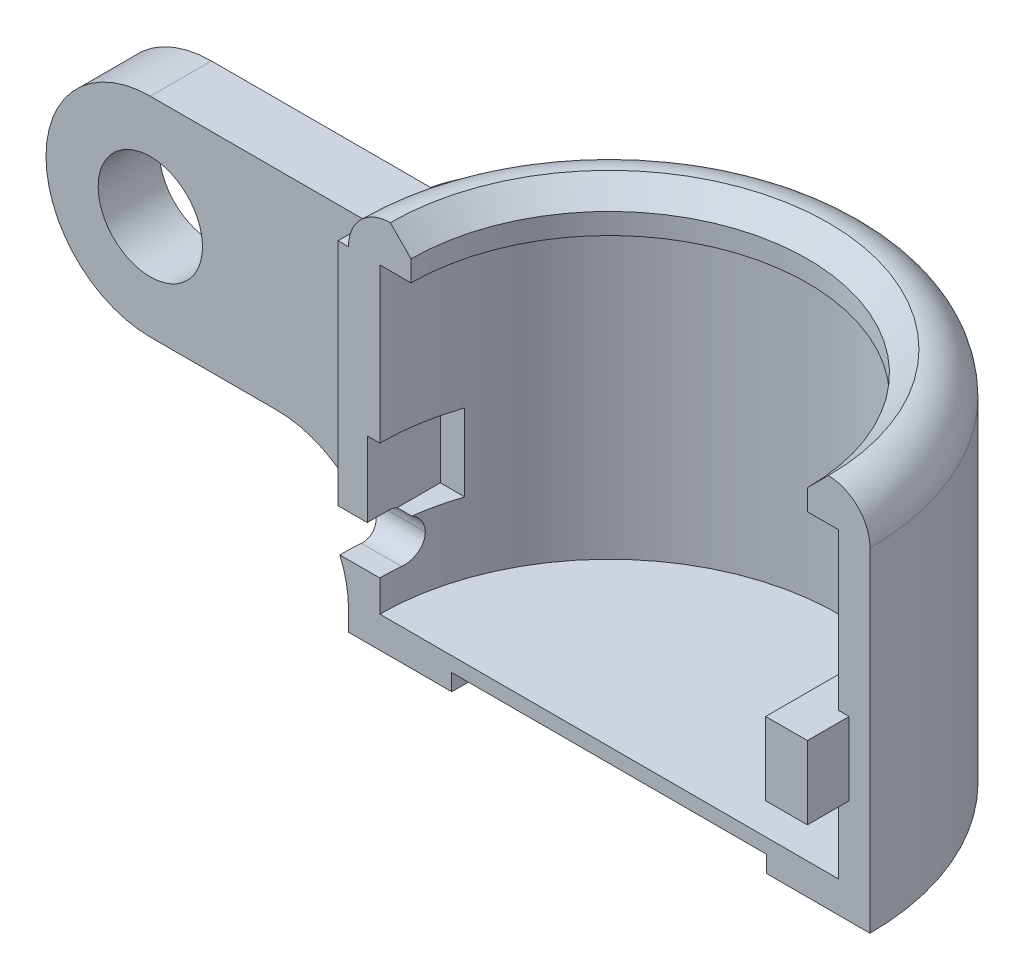
SolidWorks part; units mm, degrees
ref_plane "Plan de face" through (0, 0, 0) normal (0, 0, 1) x (1, 0, 0)
ref_plane "Plan de dessus" through (0, 0, 0) normal (0, 1, 0) x (1, 0, 0)
ref_plane "Plan de droite" through (0, 0, 0) normal (1, 0, 0) x (0, 0, -1)
sketch "Esquisse3" plane through (0, 0, 0) normal (0, 0, 1) x (1, 0, 0)
  line L0 (0, 0) -> (12.5, 0)
  line L1 (12.5, 0) -> (12.5, 18)
  line L2 (12.5, 18) -> (9.5, 18)
  line L3 (9.5, 18) -> (9.5, 16)
  line L4 (9.5, 16) -> (11, 16)
  line L5 (11, 16) -> (11, 1.5)
  line L6 (11, 1.5) -> (0, 1.5)
  line L7 (0, 1.5) -> (0, 0)
  line L8 (0, 0) -> (0, 28.6696) construction
  point P3 (9.5, 19.1495)
  point P11 (9.5, 17.9629)
  dimension "D1" = 19
  dimension "D2" = 25
  dimension "D3" = 14.5
  dimension "D4" = 2
  dimension "D5" = 1.5
  dimension "D6" = 22
revolve "Révolution1" add sketch "Esquisse3" angle 180 about L8
chamfer "Chanfrein1" distance 1 angle 45 1 edges at (0, 18, -9.5)
fillet "Congé1" radius 2 1 edges at (0, 18, -12.5)
sketch "Esquisse4" plane through (0, 0, 0) normal (1, 0, 0) x (0, 0, -1)
  line L0 (0, 0) -> (0, 3) construction
  line L1 (-2, 3) -> (2, 3)
  line L2 (-2, 3) -> (-2, 5)
  line L3 (-2, 5) -> (2, 5)
  line L4 (2, 3) -> (2, 5)
  dimension "D1" = 4
  dimension "D2" = 2
  dimension "D3" = 1.5
extrude "Enlèv. mat.-Extru.1" cut sketch "Esquisse4" against normal up to next
fillet "Congé2" radius 1 2 edges at (-11.5778, 5, -2) (-11.5778, 3, -2)
sketch "Esquisse5" plane through (0, 0, 0) normal (0, 0, 1) x (1, 0, 0)
  line L0 (11, 16) -> (11, 1.5) construction
  line L1 (9.5, 8.5) -> (11.5, 8.5)
  line L2 (9.5, 8.5) -> (9.5, 5)
  line L3 (9.5, 5) -> (11.5, 5)
  line L4 (11.5, 8.5) -> (11.5, 5)
  dimension "D1" = 3.5
  dimension "D2" = 2
  dimension "D3" = 1.5
  dimension "D4" = 3.5
extrude "Boss.-Extru.2" add sketch "Esquisse5" against normal up to surface and the other way blind 2 up to face at (-6.0789, 6.129, -2.9349)
sketch "Esquisse6" plane through (0, 0, 0) normal (0, 0, 1) x (1, 0, 0)
  line L0 (9.5, 5) -> (11.5, 5) construction
  line L1 (-11.5, 5) -> (-9.5, 5)
  line L2 (-11.5, 5) -> (-11.5, 8.5)
  line L3 (-11.5, 8.5) -> (-9.5, 8.5)
  line L4 (-9.5, 5) -> (-9.5, 8.5)
  line L5 (11.5, 8.5) -> (9.5, 8.5) construction
  line L6 (9.5, 8.5) -> (9.5, 5) construction
  line L7 (-12.5, 5) -> (-12.5, 16) construction
  line L9 (-11.6, 8.6) -> (-9.4, 8.6)
  line L10 (-11.6, 8.6) -> (-11.6, 4.9)
  line L11 (-11.6, 4.9) -> (-9.4, 4.9)
  line L12 (-9.4, 8.6) -> (-9.4, 4.9)
  point P16 (0, 0)
  point P17 (0, 0)
  dimension "D1" = 1
  dimension "D2" = 0.1
  dimension "D3" = 0.1
  dimension "D4" = 0.1
  dimension "D5" = 0.1
extrude "Enlèv. mat.-Extru.3" cut sketch "Esquisse6" against normal blind 3.5 contours L9 L12 L11 L10
sketch "Esquisse8" plane through (0, 0, 0) normal (0, -1, 0) x (1, 0, 0)
  line L2 (12.5, 0) -> (-12.5, 0) construction
  line L3 (-7.55, 0) -> (7.55, 0)
  line L4 (-7.55, 0) -> (-7.55, -2.1)
  line L5 (-7.55, -2.1) -> (7.55, -2.1)
  line L6 (7.55, 0) -> (7.55, -2.1)
  point P6 (0, 0)
  dimension "D1" = 2.1
  dimension "D2" = 15.1
extrude "Enlèv. mat.-Extru.4" cut sketch "Esquisse8" against normal blind 0.8
sketch "Esquisse9" plane through (0, 0, 0) normal (0, 1, 0) x (1, 0, 0)
  line L0 (-10.0669, 7.41) -> (-13, 7.41)
  line L1 (-13, 7.41) -> (-13, 4.43)
  line L2 (-13, 4.43) -> (-28.5, 4.43)
  line L3 (-28.5, 4.43) -> (-28.5, 1.5)
  line L4 (-28.5, 1.5) -> (-13, 1.5)
  line L5 (-13, 1.5) -> (-13, 0)
  line L6 (-13, 0) -> (-12.5, 0)
  arc A0 (12.5, 0) -> (-12.5, 0) centre (0, 0) ccw construction
  arc A1 (-12.5, 0) -> (-10.0669, 7.41) centre (0, 0) cw
  dimension "D1" = 16
  dimension "D2" = 1.5
  dimension "D3" = 2.93
  dimension "D4" = 2.98
  dimension "D5" = 0.5
extrude "Boss.-Extru.3" add sketch "Esquisse9" against normal blind 10 from vertex starting at point (-12.5, 16, 0)
fillet "Congé3" radius 5 2 edges at (-28.5, 6, -2.965) (-28.5, 16, -2.965)
sketch "Esquisse10" plane through (0, 0, -4.43) normal (0, 0, -1) x (-1, 0, 0)
  circle A0 centre (23.5, 11) radius 2.5
  arc A1 (23.5, 6) -> (28.5, 11) centre (23.5, 11) ccw construction
  dimension "D1" = 5
extrude "Enlèv. mat.-Extru.5" cut sketch "Esquisse10" against normal up to next
fillet "Congé4" radius 5 1 edges at (-10.0669, 11, -7.41)
fillet "Congé5" radius 5 1 edges at (-11.5416, 6, -4.8002)
fillet "Congé6" radius 5 1 edges at (-13, 10.6544, -7.41)
